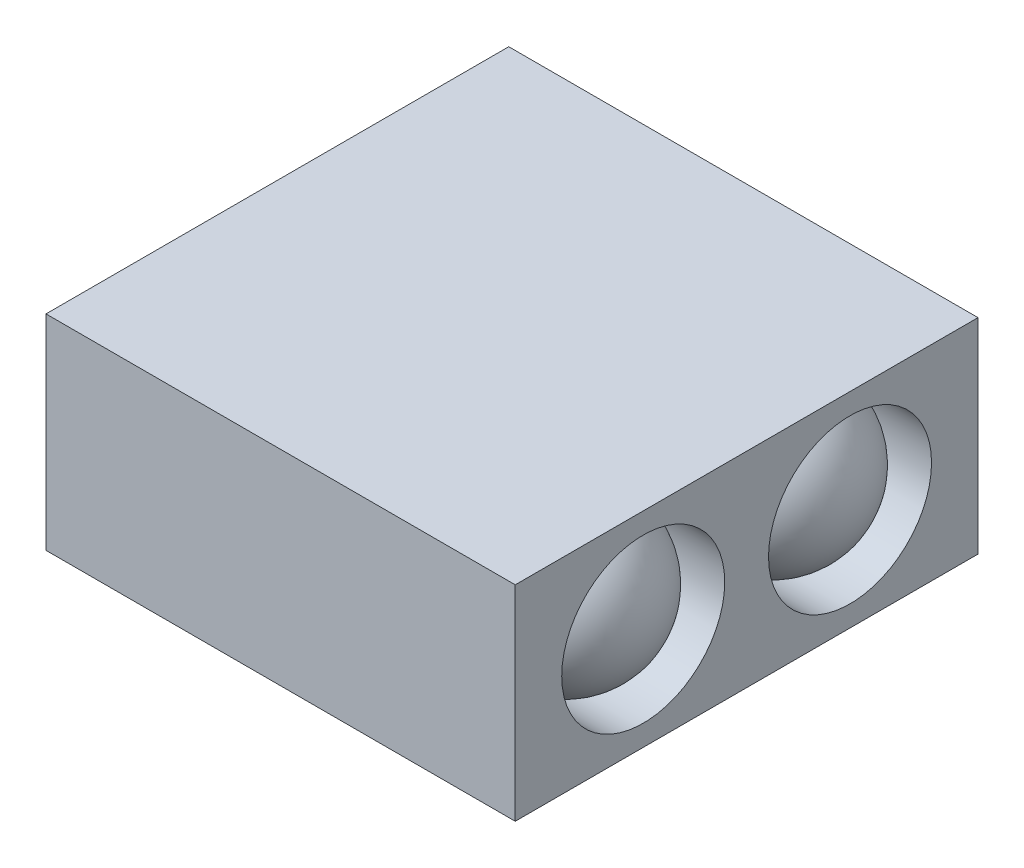
SolidWorks part; units mm, degrees
ref_plane "Front Plane" through (0, 0, 0) normal (0, 0, 1) x (1, 0, 0)
ref_plane "Top Plane" through (0, 0, 0) normal (0, 1, 0) x (1, 0, 0)
ref_plane "Right Plane" through (0, 0, 0) normal (1, 0, 0) x (0, 0, -1)
sketch "Sketch1" plane through (0, 0, 0) normal (0, 1, 0) x (1, 0, 0)
  line L1 (-181, -178.5) -> (181, -178.5)
  line L2 (-181, -178.5) -> (-181, 178.5)
  line L3 (-181, 178.5) -> (181, 178.5)
  line L4 (181, -178.5) -> (181, 178.5)
  line L5 (-181, -178.5) -> (181, 178.5) construction
  line L6 (-181, 178.5) -> (181, -178.5) construction
  point P0 (0, 0)
  dimension "D1" = 357
  dimension "D2" = 362
extrude "Boss-Extrude1" add sketch "Sketch1" along normal blind 158
sketch "Sketch2" plane through (181, 0, 0) normal (1, 0, 0) x (0, 0, -1)
  line L0 (-178.5, 79) -> (178.5, 79) construction
  line L1 (-178.5, 158) -> (-178.5, 0) construction
  line L2 (178.5, 158) -> (178.5, 0) construction
  line L3 (0, 158) -> (0, 0) construction
  line L4 (-178.5, 158) -> (178.5, 158) construction
  circle A0 centre (-79.774, 79) radius 62.8771
  circle A1 centre (79.774, 79) radius 62.8771
extrude "Cut-Extrude1" cut sketch "Sketch2" against normal blind 60
sketch "Sketch3" plane through (121, 0, 0) normal (1, 0, 0) x (0, 0, -1)
  line L0 (-79.774, 141.8771) -> (-79.774, 16.1229)
  arc A0 (-79.774, 141.8771) -> (-79.774, 16.1229) centre (-79.774, 79) ccw
revolve "Revolve1" add sketch "Sketch3" angle 180 about L0 reverse direction yes
sketch "Sketch4" plane through (121, 0, 0) normal (1, 0, 0) x (0, 0, -1)
  line L0 (79.774, 141.8771) -> (79.774, 16.1229)
  arc A0 (79.774, 141.8771) -> (79.774, 16.1229) centre (79.774, 79) ccw
revolve "Revolve2" add sketch "Sketch4" angle 180 about L0 reverse direction yes
